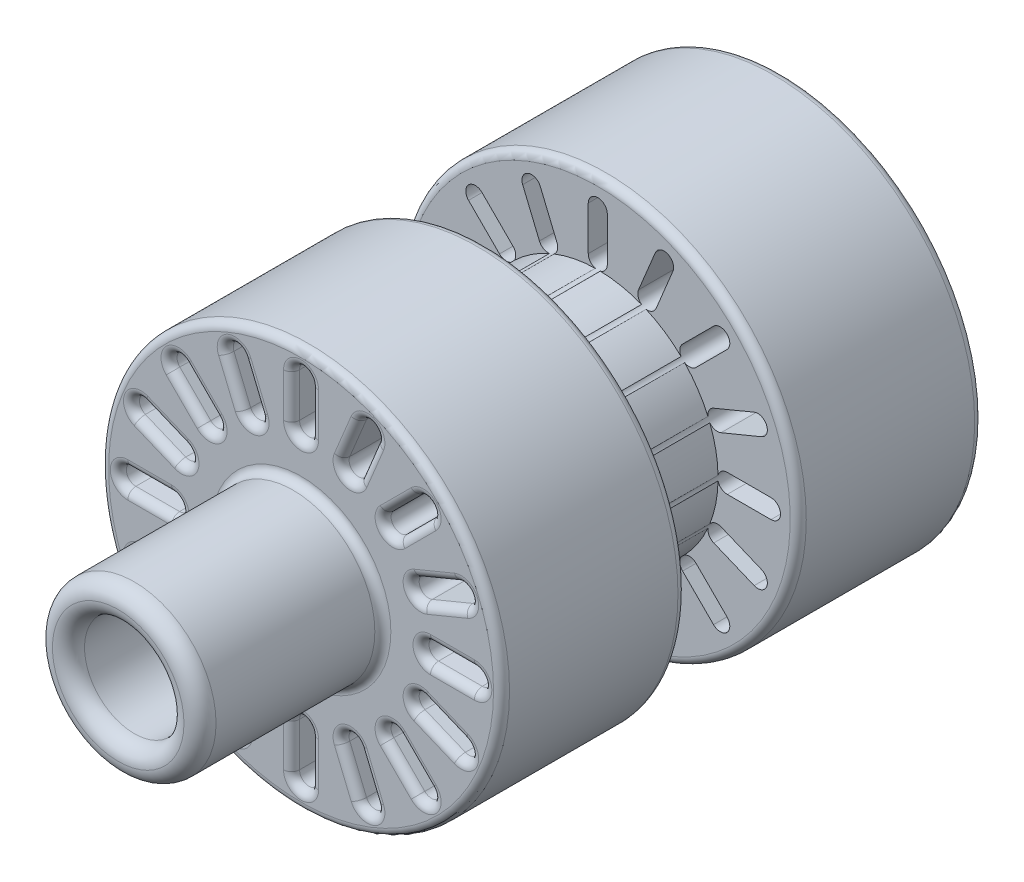
SolidWorks part; units mm, degrees
ref_plane "Front Plane" through (0, 0, 0) normal (0, 0, 1) x (1, 0, 0)
ref_plane "Top Plane" through (0, 0, 0) normal (0, 1, 0) x (1, 0, 0)
ref_plane "Right Plane" through (0, 0, 0) normal (1, 0, 0) x (0, 0, -1)
sketch "Sketch1" plane through (0, 0, 0) normal (1, 0, 0) x (0, 0, -1)
  line L0 (-15, 0) -> (15, 0)
  line L1 (-15, 5.1) -> (-15, 12.5)
  line L2 (-15, 0) -> (15, 0)
  line L3 (-15, 2) -> (-15, 3.1)
  line L4 (-15, 12.5) -> (-3.5, 12.5)
  line L5 (15, 6) -> (15, 12.5)
  line L6 (15, 0) -> (3.6, 0)
  line L8 (15, 6) -> (3.6, 6)
  line L9 (3.6, 3.1) -> (3.6, 6)
  line L10 (3.5, 12.5) -> (15, 12.5)
  line L12 (3.5, 12.5) -> (3.5, 7.5)
  line L13 (3.5, 7.5) -> (-3.5, 7.5)
  line L14 (-3.5, 12.5) -> (-3.5, 7.5)
  line L19 (3.6, 0) -> (-15, 0)
  line L21 (3.6, 3.1) -> (-15, 3.1)
  line L22 (-15, 2) -> (-15, 3.1)
  line L23 (-15, 3.1) -> (-26.4, 3.1)
  line L25 (-15, 5.1) -> (-26.4, 5.1)
  line L26 (-26.4, 3.1) -> (-26.4, 5.1)
  point P4 (0, 0)
  point P13 (0, 12.5)
  dimension "D1" = 30
  dimension "D2" = 12.5
  dimension "D3" = 11.4
  dimension "D4" = 6
  dimension "D5" = 5
  dimension "D6" = 3.1
  dimension "D7" = 11.4
  dimension "D8" = 2
  dimension "D9" = 1.5
revolve "Revolve1" add sketch "Sketch1" angle 360 about L0 region at (0, 8.8, 14.5755)
sketch "Sketch2" plane through (0, 0, -15) normal (0, 0, -1) x (-1, 0, 0)
  line L0 (0, 6) -> (0, 12.5) construction
  line L1 (0, 12.5) -> (0, 11.3) construction
  line L2 (0, 6) -> (0, 6.0726) construction
  line L3 (0, 11.3) -> (0, 10.8) construction
  line L4 (0, 6.0726) -> (0, 8.0726) construction
  line L5 (0, 10.8) -> (0, 8.0726) construction
  line L6 (0.5941, 10.8) -> (0.5941, 8.0726)
  line L7 (-0.5941, 10.8) -> (-0.5941, 8.0726)
  line L8 (3.5841, 10.2053) -> (2.5403, 7.6854)
  line L9 (4.6819, 9.7505) -> (3.6382, 7.2307)
  line L10 (4.133, 9.9779) -> (3.0892, 7.4581) construction
  line L11 (7.2166, 8.0569) -> (5.288, 6.1283)
  line L12 (8.0569, 7.2166) -> (6.1283, 5.288)
  line L13 (7.6368, 7.6368) -> (5.7082, 5.7082) construction
  line L14 (9.7505, 4.6819) -> (7.2307, 3.6382)
  line L15 (10.2053, 3.5841) -> (7.6854, 2.5403)
  line L16 (9.9779, 4.133) -> (7.4581, 3.0892) construction
  line L17 (10.8, 0.5941) -> (8.0726, 0.5941)
  line L18 (10.8, -0.5941) -> (8.0726, -0.5941)
  line L19 (10.8, 0) -> (8.0726, 0) construction
  line L20 (10.2053, -3.5841) -> (7.6854, -2.5403)
  line L21 (9.7505, -4.6819) -> (7.2307, -3.6382)
  line L22 (9.9779, -4.133) -> (7.4581, -3.0892) construction
  line L23 (8.0569, -7.2166) -> (6.1283, -5.288)
  line L24 (7.2166, -8.0569) -> (5.288, -6.1283)
  line L25 (7.6368, -7.6368) -> (5.7082, -5.7082) construction
  line L26 (4.6819, -9.7505) -> (3.6382, -7.2307)
  line L27 (3.5841, -10.2053) -> (2.5403, -7.6854)
  line L28 (4.133, -9.9779) -> (3.0892, -7.4581) construction
  line L29 (0.5941, -10.8) -> (0.5941, -8.0726)
  line L30 (-0.5941, -10.8) -> (-0.5941, -8.0726)
  line L31 (0, -10.8) -> (0, -8.0726) construction
  line L32 (-3.5841, -10.2053) -> (-2.5403, -7.6854)
  line L33 (-4.6819, -9.7505) -> (-3.6382, -7.2307)
  line L34 (-4.133, -9.9779) -> (-3.0892, -7.4581) construction
  line L35 (-7.2166, -8.0569) -> (-5.288, -6.1283)
  line L36 (-8.0569, -7.2166) -> (-6.1283, -5.288)
  line L37 (-7.6368, -7.6368) -> (-5.7082, -5.7082) construction
  line L38 (-9.7505, -4.6819) -> (-7.2307, -3.6382)
  line L39 (-10.2053, -3.5841) -> (-7.6854, -2.5403)
  line L40 (-9.9779, -4.133) -> (-7.4581, -3.0892) construction
  line L41 (-10.8, -0.5941) -> (-8.0726, -0.5941)
  line L42 (-10.8, 0.5941) -> (-8.0726, 0.5941)
  line L43 (-10.8, 0) -> (-8.0726, 0) construction
  line L44 (-10.2053, 3.5841) -> (-7.6854, 2.5403)
  line L45 (-9.7505, 4.6819) -> (-7.2307, 3.6382)
  line L46 (-9.9779, 4.133) -> (-7.4581, 3.0892) construction
  line L47 (-8.0569, 7.2166) -> (-6.1283, 5.288)
  line L48 (-7.2166, 8.0569) -> (-5.288, 6.1283)
  line L49 (-7.6368, 7.6368) -> (-5.7082, 5.7082) construction
  line L50 (-4.6819, 9.7505) -> (-3.6382, 7.2307)
  line L51 (-3.5841, 10.2053) -> (-2.5403, 7.6854)
  line L52 (-4.133, 9.9779) -> (-3.0892, 7.4581) construction
  circle A0 centre (0, 0) radius 6 construction
  circle A1 centre (0, 0) radius 12.5 construction
  arc A2 (0.5941, 10.8) -> (-0.5941, 10.8) centre (0, 10.8) ccw
  arc A3 (-0.5941, 8.0726) -> (0.5941, 8.0726) centre (0, 8.0726) ccw
  arc A4 (4.6819, 9.7505) -> (3.5841, 10.2053) centre (4.133, 9.9779) ccw
  arc A5 (2.5403, 7.6854) -> (3.6382, 7.2307) centre (3.0892, 7.4581) ccw
  arc A6 (8.0569, 7.2166) -> (7.2166, 8.0569) centre (7.6368, 7.6368) ccw
  arc A7 (5.288, 6.1283) -> (6.1283, 5.288) centre (5.7082, 5.7082) ccw
  arc A8 (10.2053, 3.5841) -> (9.7505, 4.6819) centre (9.9779, 4.133) ccw
  arc A9 (7.2307, 3.6382) -> (7.6854, 2.5403) centre (7.4581, 3.0892) ccw
  arc A10 (10.8, -0.5941) -> (10.8, 0.5941) centre (10.8, 0) ccw
  arc A11 (8.0726, 0.5941) -> (8.0726, -0.5941) centre (8.0726, 0) ccw
  arc A12 (9.7505, -4.6819) -> (10.2053, -3.5841) centre (9.9779, -4.133) ccw
  arc A13 (7.6854, -2.5403) -> (7.2307, -3.6382) centre (7.4581, -3.0892) ccw
  arc A14 (7.2166, -8.0569) -> (8.0569, -7.2166) centre (7.6368, -7.6368) ccw
  arc A15 (6.1283, -5.288) -> (5.288, -6.1283) centre (5.7082, -5.7082) ccw
  arc A16 (3.5841, -10.2053) -> (4.6819, -9.7505) centre (4.133, -9.9779) ccw
  arc A17 (3.6382, -7.2307) -> (2.5403, -7.6854) centre (3.0892, -7.4581) ccw
  arc A18 (-0.5941, -10.8) -> (0.5941, -10.8) centre (0, -10.8) ccw
  arc A19 (0.5941, -8.0726) -> (-0.5941, -8.0726) centre (0, -8.0726) ccw
  arc A20 (-4.6819, -9.7505) -> (-3.5841, -10.2053) centre (-4.133, -9.9779) ccw
  arc A21 (-2.5403, -7.6854) -> (-3.6382, -7.2307) centre (-3.0892, -7.4581) ccw
  arc A22 (-8.0569, -7.2166) -> (-7.2166, -8.0569) centre (-7.6368, -7.6368) ccw
  arc A23 (-5.288, -6.1283) -> (-6.1283, -5.288) centre (-5.7082, -5.7082) ccw
  arc A24 (-10.2053, -3.5841) -> (-9.7505, -4.6819) centre (-9.9779, -4.133) ccw
  arc A25 (-7.2307, -3.6382) -> (-7.6854, -2.5403) centre (-7.4581, -3.0892) ccw
  arc A26 (-10.8, 0.5941) -> (-10.8, -0.5941) centre (-10.8, 0) ccw
  arc A27 (-8.0726, -0.5941) -> (-8.0726, 0.5941) centre (-8.0726, 0) ccw
  arc A28 (-9.7505, 4.6819) -> (-10.2053, 3.5841) centre (-9.9779, 4.133) ccw
  arc A29 (-7.6854, 2.5403) -> (-7.2307, 3.6382) centre (-7.4581, 3.0892) ccw
  arc A30 (-7.2166, 8.0569) -> (-8.0569, 7.2166) centre (-7.6368, 7.6368) ccw
  arc A31 (-6.1283, 5.288) -> (-5.288, 6.1283) centre (-5.7082, 5.7082) ccw
  arc A32 (-3.5841, 10.2053) -> (-4.6819, 9.7505) centre (-4.133, 9.9779) ccw
  arc A33 (-3.6382, 7.2307) -> (-2.5403, 7.6854) centre (-3.0892, 7.4581) ccw
  point P11 (0, 9.4363)
  point P16 (0, 6.0726)
  point P17 (0, 0)
  point P18 (0, 0)
  point P21 (3.6111, 8.718)
  point P28 (6.6725, 6.6725)
  point P35 (8.718, 3.6111)
  point P42 (9.4363, 0)
  point P49 (8.718, -3.6111)
  point P56 (6.6725, -6.6725)
  point P63 (3.6111, -8.718)
  point P70 (0, -9.4363)
  point P77 (-3.6111, -8.718)
  point P84 (-6.6725, -6.6725)
  point P91 (-8.718, -3.6111)
  point P98 (-9.4363, 0)
  point P105 (-8.718, 3.6111)
  point P112 (-6.6725, 6.6725)
  point P119 (-3.6111, 8.718)
  point P124 (0, 0)
  dimension "D1" = 1.2
  dimension "D2" = 0.5
  dimension "D3" = 2
  dimension "D4" = 16
extrude "Cut-Extrude1" cut sketch "Sketch2" against normal blind 86
fillet "Fillet3" radius 0.5 66 edges at (6, 0, -15) (12.5, 0, -15) (0, 7.4784, -15) (-0.5941, 9.4363, -15) (0, 11.3941, -15) (0.5941, 9.4363, -15) (-7.4784, 0, -15) (-9.4363, -0.5941, -15) (-11.3941, 0, -15) (-9.4363, 0.5941, -15) (-6.9092, 2.8619, -15) (-8.9454, 3.0622, -15) (-10.5268, 4.3603, -15) (-8.4906, 4.16, -15) (-2.8619, 6.9092, -15) (-4.16, 8.4906, -15) (-4.3603, 10.5268, -15) (-3.0622, 8.9454, -15) (-5.288, 5.288, -15) (-7.0926, 6.2523, -15) (-8.0569, 8.0569, -15) (-6.2523, 7.0926, -15) (0, -7.4784, -15) (0.5941, -9.4363, -15) (0, -11.3941, -15) (-0.5941, -9.4363, -15) (-2.8619, -6.9092, -15) (-3.0622, -8.9454, -15) (-4.3603, -10.5268, -15) (-4.16, -8.4906, -15) (-6.9092, -2.8619, -15) (-8.4906, -4.16, -15) (-10.5268, -4.3603, -15) (-8.9454, -3.0622, -15) (-5.288, -5.288, -15) (-6.2523, -7.0926, -15) (-8.0569, -8.0569, -15) (-7.0926, -6.2523, -15) (7.4784, 0, -15) (9.4363, 0.5941, -15) (11.3941, 0, -15) (9.4363, -0.5941, -15) (6.9092, -2.8619, -15) (8.9454, -3.0622, -15) (10.5268, -4.3603, -15) (8.4906, -4.16, -15) (2.8619, -6.9092, -15) (4.16, -8.4906, -15) (4.3603, -10.5268, -15) (3.0622, -8.9454, -15) (5.288, -5.288, -15) (7.0926, -6.2523, -15) (8.0569, -8.0569, -15) (6.2523, -7.0926, -15) (2.8619, 6.9092, -15) (3.0622, 8.9454, -15) (4.3603, 10.5268, -15) (4.16, 8.4906, -15) (6.9092, 2.8619, -15) (8.4906, 4.16, -15) (10.5268, 4.3603, -15) (8.9454, 3.0622, -15) (5.288, 5.288, -15) (6.2523, 7.0926, -15) (8.0569, 8.0569, -15) (7.0926, 6.2523, -15)
fillet "Fillet5" radius 0.5 68 edges at (5.1, 0, 15) (12.5, 0, 15) (-0.5941, 9.4363, 15) (0, 7.4784, 15) (0.5941, 9.4363, 15) (0, 11.3941, 15) (-9.4363, -0.5941, 15) (-7.4784, 0, 15) (-9.4363, 0.5941, 15) (-11.3941, 0, 15) (-8.9454, 3.0622, 15) (-6.9092, 2.8619, 15) (-8.4906, 4.16, 15) (-10.5268, 4.3603, 15) (-4.16, 8.4906, 15) (-2.8619, 6.9092, 15) (-3.0622, 8.9454, 15) (-4.3603, 10.5268, 15) (-7.0926, 6.2523, 15) (-5.288, 5.288, 15) (-6.2523, 7.0926, 15) (-8.0569, 8.0569, 15) (0.5941, -9.4363, 15) (0, -7.4784, 15) (-0.5941, -9.4363, 15) (0, -11.3941, 15) (-3.0622, -8.9454, 15) (-2.8619, -6.9092, 15) (-4.16, -8.4906, 15) (-4.3603, -10.5268, 15) (-8.4906, -4.16, 15) (-6.9092, -2.8619, 15) (-8.9454, -3.0622, 15) (-10.5268, -4.3603, 15) (-6.2523, -7.0926, 15) (-5.288, -5.288, 15) (-7.0926, -6.2523, 15) (-8.0569, -8.0569, 15) (9.4363, 0.5941, 15) (7.4784, 0, 15) (9.4363, -0.5941, 15) (11.3941, 0, 15) (8.9454, -3.0622, 15) (6.9092, -2.8619, 15) (8.4906, -4.16, 15) (10.5268, -4.3603, 15) (4.16, -8.4906, 15) (2.8619, -6.9092, 15) (3.0622, -8.9454, 15) (4.3603, -10.5268, 15) (7.0926, -6.2523, 15) (5.288, -5.288, 15) (6.2523, -7.0926, 15) (8.0569, -8.0569, 15) (3.0622, 8.9454, 15) (2.8619, 6.9092, 15) (4.16, 8.4906, 15) (4.3603, 10.5268, 15) (8.4906, 4.16, 15) (6.9092, 2.8619, 15) (8.9454, 3.0622, 15) (10.5268, 4.3603, 15) (6.2523, 7.0926, 15) (5.288, 5.288, 15) (7.0926, 6.2523, 15) (8.0569, 8.0569, 15) (12.5, 0, -3.5) (12.5, 0, 3.5)
fillet "Fillet6" radius 1 2 edges at (3.1, 0, 26.4) (5.1, 0, 26.4)
